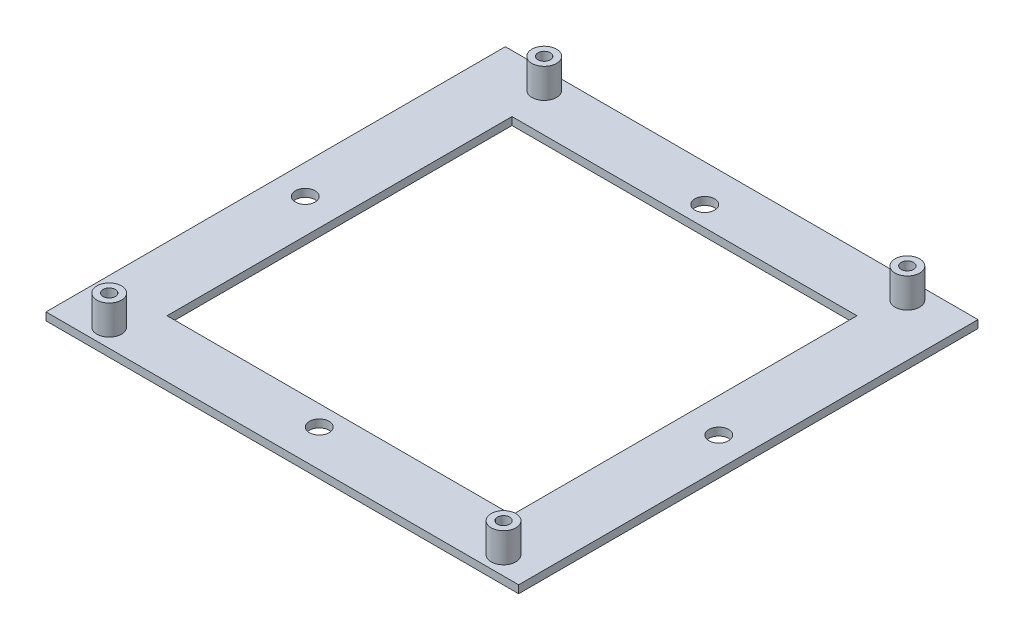
SolidWorks part; units mm, degrees
material "5052-H32"
ref_plane "Front Plane" through (0, 0, 0) normal (0, 0, 1) x (1, 0, 0)
ref_plane "Top Plane" through (0, 0, 0) normal (0, 1, 0) x (1, 0, 0)
ref_plane "Right Plane" through (0, 0, 0) normal (1, 0, 0) x (0, 0, -1)
sketch "Sketch1" plane through (0, 0, 0) normal (0, 1, 0) x (1, 0, 0)
  line L1 (-47.95, -46.6) -> (47.95, -46.6)
  line L2 (-47.95, -46.6) -> (-47.95, 46.6)
  line L3 (-47.95, 46.6) -> (47.95, 46.6)
  line L4 (47.95, -46.6) -> (47.95, 46.6)
  line L5 (-47.95, -46.6) -> (47.95, 46.6) construction
  line L6 (-47.95, 46.6) -> (47.95, -46.6) construction
  line L7 (-35, -35) -> (35, -35)
  line L8 (-35, -35) -> (-35, 35)
  line L9 (-35, 35) -> (35, 35)
  line L10 (35, -35) -> (35, 35)
  line L11 (-35, -35) -> (35, 35) construction
  line L12 (-35, 35) -> (35, -35) construction
  circle A0 centre (0, 39.1) radius 2
  circle A1 centre (41.95, 0) radius 2
  circle A2 centre (0, -39.1) radius 2
  circle A3 centre (-41.95, 0) radius 2
  point P0 (0, 0)
  point P6 (0, 0)
  point P11 (0, 39.1)
  point P12 (0, -39.1)
  point P13 (41.95, 0)
  point P14 (-41.95, 0)
extrude "Boss-Extrude1" add sketch "Sketch1" along normal blind 1.58
sketch "Sketch2" plane through (0, 1.58, 0) normal (0, 1, 0) x (1, 0, 0)
  circle A0 centre (37.355, 42.8635) radius 2.5
  circle A1 centre (-36.325, 42.8625) radius 2.5
  circle A2 centre (-38.865, -42.8625) radius 2.5
  circle A3 centre (41.145, -42.8625) radius 2.5
  point P0 (37.355, 42.8635)
extrude "Boss-Extrude2" add sketch "Sketch2" along normal blind 6
hole_wizard "M3x0.5 Tapped Hole2" positions "3DSketch2" profile "Sketch4" tap size "M3x0.5" standard "ANSI Metric"
sketch3d "3DSketch2"
  line L0 (-36.325, 7.58, -42.8625) -> (-36.325, 1.58, -42.8625) construction
  line L1 (-38.865, 7.58, 42.8625) -> (-38.865, 1.58, 42.8625) construction
  line L2 (41.145, 7.58, 42.8625) -> (41.145, 1.58, 42.8625) construction
  line L3 (37.355, 7.58, -42.8635) -> (37.355, 1.58, -42.8635) construction
  point P0 (-36.325, 7.58, -42.8625)
  point P4 (-38.865, 7.58, 42.8625)
  point P8 (41.145, 7.58, 42.8625)
  point P12 (37.355, 7.58, -42.8635)
sketch "Sketch4" plane through (-36.325, 7.58, -42.8625) normal (1, 0, 0) x (0, 0, 1)
  line L0 (0, 0) -> (0, 6.7511)
  line L1 (0, 6.7511) -> (1.25, 6)
  line L2 (1.25, 6) -> (1.25, 0)
  line L5 (1.25, 0) -> (0, 0)
  line L10 (0, 6.7511) -> (-1.25, 6) construction
  line L11 (0, -6.35) -> (0, 107.95) construction
  dimension "Tap Drill Dia." = 2.5
  dimension "Tap Drill Depth" = 6
  dimension "Drill Angle" = 118
cosmetic thread "Hole Thread5" parameters "D1"=6, "D2"=3
cosmetic thread "Hole Thread6" parameters "D1"=6, "D2"=3
cosmetic thread "Hole Thread7" parameters "D1"=6, "D2"=3
cosmetic thread "Hole Thread8" parameters "D1"=6, "D2"=3
